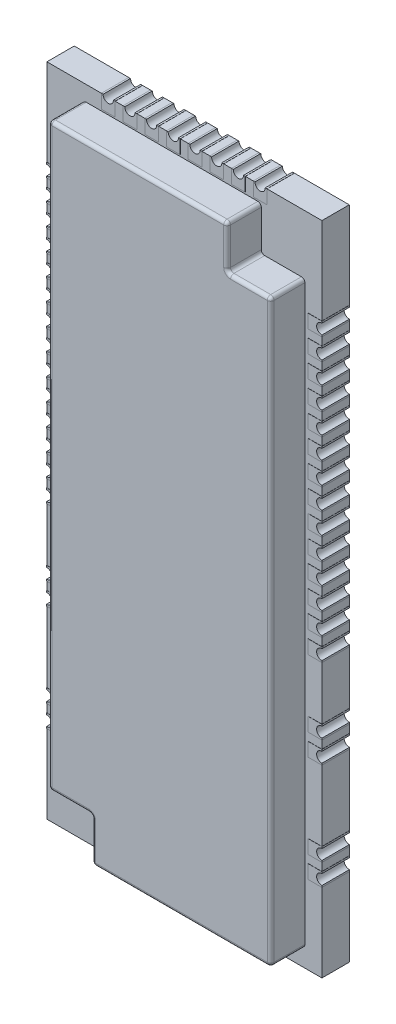
SolidWorks part; units mm, degrees
ref_plane "Plan de face" through (0, 0, 0) normal (0, 0, 1) x (1, 0, 0)
ref_plane "Plan de dessus" through (0, 0, 0) normal (0, 1, 0) x (1, 0, 0)
ref_plane "Plan de droite" through (0, 0, 0) normal (1, 0, 0) x (0, 0, -1)
sketch "Esquisse1" plane through (0, 0, 0) normal (0, 0, 1) x (1, 0, 0)
  line L1 (0, 0) -> (16.1, 0)
  line L2 (0, 0) -> (0, 38.4)
  line L3 (0, 38.4) -> (16.1, 38.4)
  line L4 (16.1, 0) -> (16.1, 38.4)
  dimension "D1" = 38.4
  dimension "D2" = 16.1
extrude "Boss.-Extru.1" add sketch "Esquisse1" along normal blind 1.6
sketch "Esquisse7" plane through (0, 0, 1.6) normal (0, 0, 1) x (1, 0, 0)
  line L0 (16.1, 0) -> (16.1, 38.4) construction
  line L1 (16.1, 33.31) -> (15.3, 33.31)
  line L2 (16.1, 33.31) -> (16.1, 32.51)
  line L3 (16.1, 32.51) -> (15.3, 32.51)
  line L4 (15.3, 33.31) -> (15.3, 32.51)
extrude "Boss.-Extru.4" add sketch "Esquisse7" along normal blind 0.01
sketch "Esquisse9" plane through (0, 0, 1.6) normal (0, 0, 1) x (1, 0, 0)
  line L0 (16.1, 38.4) -> (0, 38.4) construction
  line L1 (12.89, 38.4) -> (12.09, 38.4)
  line L2 (12.89, 38.4) -> (12.89, 37.6)
  line L3 (12.89, 37.6) -> (12.09, 37.6)
  line L4 (12.09, 38.4) -> (12.09, 37.6)
extrude "Boss.-Extru.6" add sketch "Esquisse9" along normal blind 0.01
pattern_linear "Répétition linéaire6" count 8 spacing 1.27 along (-1, 0, 0) of "Boss.-Extru.6"
pattern_linear "Répétition linéaire4" count 14 spacing 1.27 along (0, -1, 0) count 2 spacing 15.3 along (-1, 0, 0) of "Boss.-Extru.4"
sketch "Esquisse10" plane through (0, 38.4, 0) normal (0, 1, 0) x (1, 0, 0)
  line L1 (12.89, -1.61) -> (12.0898, -1.61)
  line L2 (12.89, -1.61) -> (12.89, -0.0352)
  line L3 (12.89, -0.0352) -> (12.0898, -0.0352)
  line L4 (12.0898, -1.61) -> (12.0898, -0.0352)
extrude "Boss.-Extru.7" add sketch "Esquisse10" along normal blind 0.01
pattern_linear "Répétition linéaire7" count 8 spacing 1.27 along (-1, 0, 0) of "Boss.-Extru.7"
sketch "Esquisse8" plane through (0, 0, 0) normal (-1, 0, 0) x (0, 0, 1)
  line L0 (0, 38.4) -> (0, 0) construction
  line L1 (1.61, 33.31) -> (0, 33.31)
  line L2 (1.61, 33.31) -> (1.61, 32.5102)
  line L3 (1.61, 32.5102) -> (0, 32.5102)
  line L4 (0, 33.31) -> (0, 32.5102)
extrude "Boss.-Extru.5" add sketch "Esquisse8" along normal blind 0.01
pattern_linear "Répétition linéaire5" count 14 spacing 1.27 along (0, -1, 0) count 2 spacing 16.11 along (1, 0, 0) of "Boss.-Extru.5"
sketch "Esquisse11" plane through (0, 0, 1.6) normal (0, 0, 1) x (1, 0, 0)
  line L0 (0, 16) -> (0, 0) construction
  line L1 (0, 12.87) -> (0.8, 12.87)
  line L2 (0, 12.87) -> (0, 12.07)
  line L3 (0, 12.07) -> (0.8, 12.07)
  line L4 (0.8, 12.87) -> (0.8, 12.07)
  line L6 (0, 11.6) -> (0.8, 11.6)
  line L7 (0, 11.6) -> (0, 10.8)
  line L8 (0, 10.8) -> (0.8, 10.8)
  line L9 (0.8, 11.6) -> (0.8, 10.8)
  line L11 (0, 6.67) -> (0.8, 6.67)
  line L12 (0, 6.67) -> (0, 5.87)
  line L13 (0, 5.87) -> (0.8, 5.87)
  line L14 (0.8, 6.67) -> (0.8, 5.87)
  line L16 (0, 5.4) -> (0.8, 5.4)
  line L17 (0, 5.4) -> (0, 4.6)
  line L18 (0, 4.6) -> (0.8, 4.6)
  line L19 (0.8, 5.4) -> (0.8, 4.6)
  point P10 (0, 0)
  point P11 (0, 0)
  point P24 (0, 0)
  point P29 (0, 0)
extrude "Boss.-Extru.8" add sketch "Esquisse11" along normal blind 0.01
sketch "Esquisse12" plane through (0, 0, 0) normal (-1, 0, 0) x (0, 0, 1)
  line L0 (0, 16.0002) -> (0, 0) construction
  line L1 (0, 12.87) -> (1.61, 12.87)
  line L2 (0, 12.87) -> (0, 12.07)
  line L3 (0, 12.07) -> (1.61, 12.07)
  line L4 (1.61, 12.87) -> (1.61, 12.07)
  point P7 (1.61, 12.87)
extrude "Boss.-Extru.9" add sketch "Esquisse12" along normal blind 0.01
pattern_linear "Répétition linéaire8" count 2 spacing 1.27 along (0, -1, 0) count 2 spacing 16.11 along (1, 0, 0) of "Boss.-Extru.9"
pattern_linear "Répétition linéaire9" count 2 spacing 6.2 along (0, -1, 0) of "Répétition linéaire8"
sketch "Esquisse2" plane through (0, 0, 1.6) normal (0, 0, 1) x (1, 0, 0)
  line L0 (0, 38.4) -> (0, 33.31) construction
  line L1 (0, 0) -> (16.1, 0) construction
  circle A0 centre (0, 5) radius 0.3
  circle A1 centre (0, 6.27) radius 0.3
  circle A2 centre (0, 11.2) radius 0.3
  circle A3 centre (0, 12.47) radius 0.3
  dimension "D1" = 5
  dimension "D2" = 1.27
  dimension "D3" = 11.2
  dimension "D4" = 1.27
extrude "Enlèv. mat.-Extru.1" cut sketch "Esquisse2" against normal blind 1.6 and the other way blind 0.1
pattern_linear "Répétition linéaire10" count 2 spacing 15.3 along (1, 0, 0) of "Boss.-Extru.8"
pattern_linear "Répétition linéaire1" count 14 spacing 16.1 along (1, 0, 0) of "Enlèv. mat.-Extru.1"
sketch "Esquisse3" plane through (0, 0, 1.6) normal (0, 0, 1) x (1, 0, 0)
  line L0 (0, 38.4) -> (0, 33.31) construction
  line L1 (0, 0) -> (16.1, 0) construction
  circle A0 centre (0, 16.4) radius 0.3
  dimension "D1" = 16.4
extrude "Enlèv. mat.-Extru.2" cut sketch "Esquisse3" against normal blind 1.6 and the other way blind 0.1
pattern_linear "Répétition linéaire2" count 2 spacing 16.1 along (1, 0, 0) count 14 spacing 1.27 along (0, 1, 0) of "Enlèv. mat.-Extru.2"
sketch "Esquisse4" plane through (0, 0, 1.6) normal (0, 0, 1) x (1, 0, 0)
  line L0 (16.1, 38.4) -> (12.89, 38.4) construction
  line L1 (0, 38.4) -> (0, 33.31) construction
  circle A0 centre (3.6, 38.4) radius 0.3
  dimension "D1" = 3.6
extrude "Enlèv. mat.-Extru.3" cut sketch "Esquisse4" against normal blind 1.6 and the other way blind 0.1
pattern_linear "Répétition linéaire3" count 8 spacing 1.27 along (1, 0, 0) of "Enlèv. mat.-Extru.3"
sketch "Esquisse5" plane through (0, 0, 1.6) normal (0, 0, 1) x (1, 0, 0)
  line L1 (2.1, 37.5) -> (15.1, 37.5)
  line L2 (2.1, 37.5) -> (2.1, 1)
  line L3 (2.1, 1) -> (15.1, 1)
  line L4 (15.1, 37.5) -> (15.1, 1)
  line L5 (0, 0) -> (16.1, 0) construction
  line L6 (16.1, 33.31) -> (16.1, 38.4) construction
  dimension "D1" = 13
  dimension "D2" = 36.5
  dimension "D3" = 1
  dimension "D4" = 1
extrude "Boss.-Extru.2" add sketch "Esquisse5" along normal blind 2
sketch "Esquisse6" plane through (0, 0, 3.6) normal (0, 0, 1) x (1, 0, 0)
  line L1 (2.1, 1) -> (4.65, 1)
  line L2 (2.1, 1) -> (2.1, 3.55)
  line L3 (2.1, 3.55) -> (4.65, 3.55)
  line L4 (4.65, 1) -> (4.65, 3.55)
  line L5 (15.1, 37.5) -> (12.55, 37.5)
  line L6 (15.1, 37.5) -> (15.1, 34.95)
  line L7 (15.1, 34.95) -> (12.55, 34.95)
  line L8 (12.55, 37.5) -> (12.55, 34.95)
  dimension "D1" = 2.55
  dimension "D2" = 2.55
  dimension "D3" = 2.55
  dimension "D4" = 2.55
extrude "Enlèv. mat.-Extru.4" cut sketch "Esquisse6" against normal blind 2
fillet "Congé1" radius 0.2 16 edges at (2.1, 20.525, 3.6) (7.325, 37.5, 3.6) (12.55, 36.225, 3.6) (13.825, 34.95, 3.6) (15.1, 17.975, 3.6) (9.875, 1, 3.6) (4.65, 2.275, 3.6) (3.375, 3.55, 3.6) (2.1, 37.5, 2.6) (12.55, 37.5, 2.6) (12.55, 34.95, 2.6) (15.1, 34.95, 2.6) (15.1, 1, 2.6) (4.65, 1, 2.6) (4.65, 3.55, 2.6) (2.1, 3.55, 2.6)
